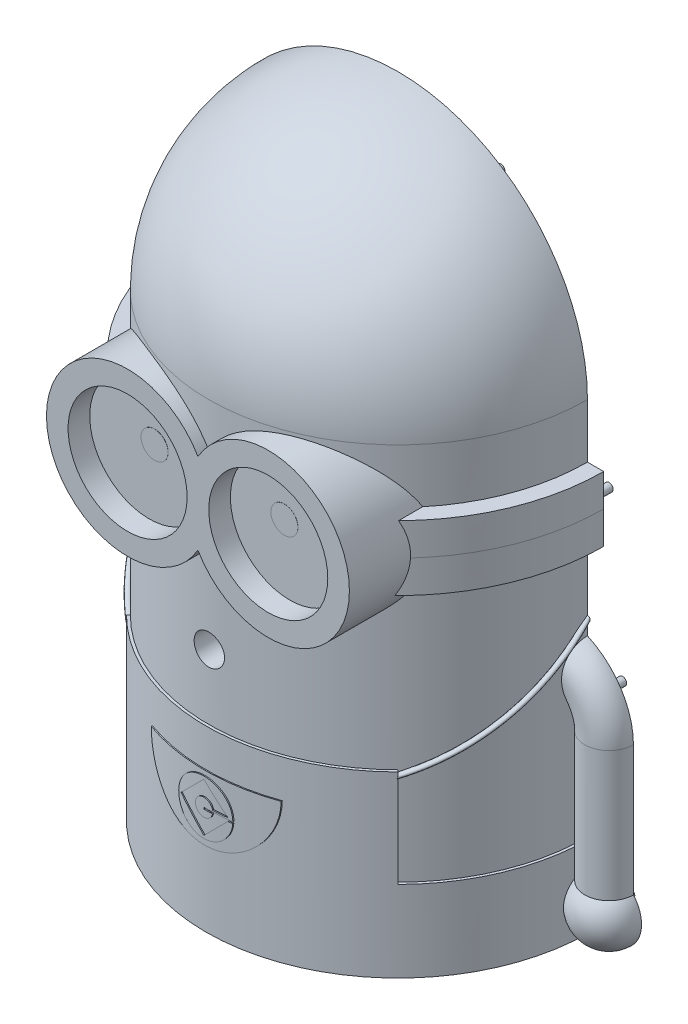
SolidWorks part; units mm, degrees
note: '?' marks a value the reader was unsure of.
material "ABS"
ref_plane "Front Plane" through (0, 0, 0) normal (0, 0, 1) x (1, 0, 0)
ref_plane "Top Plane" through (0, 0, 0) normal (0, 1, 0) x (1, 0, 0)
ref_plane "Right Plane" through (0, 0, 0) normal (1, 0, 0) x (0, 0, -1)
sketch "Sketch1" plane through (0, 0, 0) normal (0, 0, 1) x (1, 0, 0)
  line L0 (0, 0) -> (0, 101.6)
  line L1 (0, 0) -> (-44.45, 0)
  line L2 (55, 0) -> (-55, 0) construction
  line L3 (-44.45, 0) -> (-44.45, 57.15)
  line L4 (0, 72.4689) -> (0, -18.7691) construction
  arc A0 (-44.45, 57.15) -> (0, 101.6) centre (0, 57.15) cw
  dimension "D1" = 101.6
  dimension "D2" = 88.9
revolve "Body&HeadRevolve" add sketch "Sketch1" angle 360 about L4
sketch "Sketch2" plane through (0, 0, 0) normal (0, -1, 0) x (1, 0, 0)
  circle A0 centre (0, 0) radius 44.45 construction
  circle A1 centre (0, 0) radius 44.45
extrude "LowerBodyBoss-Extrude" add sketch "Sketch2" along normal blind 50.8
ref_axis "BodyAxis" through (0, -164.851, 0) along (0, 1, 0)?
ref_axis "ShoulderAxis" through (62.865, 0, 0) along (-1, 0, 0)?
sketch "Sketch4" plane through (0, 0, 0) normal (0, 0, 1) x (1, 0, 0)
  line L0 (62.865, 0) -> (-62.865, 0) construction
  line L1 (-49.53, -7.62) -> (-49.53, -40.64)
  line L2 (-36.83, -95.5054) -> (-36.83, 92.9181) construction
  line L3 (0, -164.851) -> (0, 57.15) construction
  arc A0 (-36.83, 5.08) -> (-49.53, -7.62) centre (-36.83, -7.62) ccw
  dimension "D2" = 12.7
  dimension "D1" = 33.02
  dimension "D3" = 36.83
  dimension "D4" = 5.08
ref_plane "WristPlane" through (0, -40.64, 0) normal (0, 1, 0) x (1, 0, 0)
sketch "Sketch5" plane through (0, -40.64, 0) normal (0, 1, 0) x (1, 0, 0)
  circle A0 centre (-49.53, 0) radius 5.715
  dimension "D1" = 11.43
sweep "ArmSweep" add profiles "Sketch5" path "Sketch4"
ref_axis "ArmAxis" through (-49.53, -7.62, 0) along (0, -1, 0)
sketch "Sketch7" plane through (0, 0, 0) normal (0, 0, 1) x (1, 0, 0)
  line L0 (-49.53, -7.62) -> (-49.53, -54.1089) construction
  line L1 (62.865, 0) -> (-62.865, 0) construction
  line L2 (-49.53, -35.56) -> (-49.53, -50.8)
  arc A0 (-49.53, -50.8) -> (-49.53, -35.56) centre (-49.53, -43.18) cw
  dimension "D1" = 7.62
  dimension "D2" = 43.18
revolve "HandRevolve" add sketch "Sketch7" angle 360 about axis through (-49.53, -7.62, 0) along (0, -1, 0)
mirror "ArmMirror" about plane through (0, 0, 0) normal (1, 0, 0) of "ArmSweep", "HandRevolve"
sketch "Sketch15" plane through (0, 0, 0) normal (0, 0, 1) x (1, 0, 0)
  line L0 (-16.51, 37.338) -> (0, 37.338) construction
  line L1 (0, -28.6385) -> (0, 28.6385) construction
  line L2 (16.51, 37.338) -> (0, 37.338) construction
  line L3 (-44.45, 57.15) -> (44.45, 57.15) construction
  arc A0 (0, 46.8418) -> (0, 27.8342) centre (-16.51, 37.338) ccw
  arc A1 (0, 27.8342) -> (0, 46.8418) centre (16.51, 37.338) ccw
  dimension "D1" = 38.1
  dimension "D2" = 16.51
  dimension "D3" = 19.812
extrude "GoggleBoss-Extrude" add sketch "Sketch15" along normal blind 46.99
sketch "Sketch16" plane through (0, 0, 46.99) normal (0, 0, 1) x (1, 0, 0)
  circle A0 centre (-16.51, 37.338) radius 13.97
  circle A1 centre (16.51, 37.338) radius 13.97
  arc A2 (0, 46.8418) -> (0, 27.8342) centre (-16.51, 37.338) ccw construction
  arc A3 (0, 27.8342) -> (0, 46.8418) centre (16.51, 37.338) ccw construction
  dimension "D1" = 5.08
extrude "LensCut-Extrude" cut sketch "Sketch16" against normal blind 5.08
sketch "Sketch17" plane through (0, 0, 41.91) normal (0, 0, 1) x (1, 0, 0)
  line L0 (-44.45, 57.15) -> (44.45, 57.15) construction
  line L1 (0, -28.6385) -> (0, 28.6385) construction
  circle A0 centre (-15.24, 39.116) radius 3.175
  dimension "D1" = 6.35
  dimension "D2" = 18.034
  dimension "D3" = 15.24
extrude "PupilBoss-Extrude" add sketch "Sketch17" along normal blind 0.0254
mirror "PupilMirror" about plane through (0, 0, 0) normal (1, 0, 0) of "PupilBoss-Extrude"
ref_plane "GogglePlane" through (0, 36.83, 0) normal (0, 1, 0) x (1, 0, 0)
sketch "Sketch19" plane through (0, 36.83, 0) normal (0, 1, 0) x (1, 0, 0)
  line L1 (0, 0) -> (31.4309, -31.4309)
  line L2 (0, -28.6385) -> (0, 28.6385) construction
  line L3 (0, 0) -> (0, 44.45) construction
  arc A0 (31.4309, -31.4309) -> (0, 44.45) centre (0, 0) ccw
  circle A1 centre (0, 0) radius 44.45 construction
  dimension "D2" = 45
sketch "Sketch20" plane through (0, 0, 0) normal (1, 0, 0) x (0, 0, -1)
  line L0 (44.45, 36.83) -> (44.45, 44.45)
  line L1 (44.45, 36.83) -> (-31.4309, 36.83) construction
  line L2 (44.45, -50.8) -> (44.45, 57.15) construction
  line L3 (44.45, 44.45) -> (48.26, 44.45)
  line L4 (48.26, 44.45) -> (48.26, 36.83)
  line L5 (28.6385, 36.83) -> (-28.6385, 36.83) construction
  line L6 (48.26, 36.83) -> (44.45, 36.83)
  dimension "D1" = 3.81
  dimension "D2" = 7.62
sweep "GoogleStrapSweep" add profiles "Sketch20" path "Sketch19"
mirror "StrapTopMirror" about plane through (0, 0, 0) normal (1, 0, 0) of "GoogleStrapSweep"
mirror "StrapBottomMirror" about plane through (0, 36.83, 0) normal (0, 1, 0) of "StrapTopMirror", "GoogleStrapSweep"
ref_plane "TopPantPlane" through (0, -10.16, 0) normal (0, 1, 0) x (1, 0, 0)
sketch "Sketch21" plane through (0, -10.16, 0) normal (0, 1, 0) x (1, 0, 0)
  line L0 (0, 0) -> (-31.8799, -31.8799) construction
  line L1 (0, 0) -> (0, -45.085) construction
  arc A0 (-31.8799, -31.8799) -> (0, -45.085) centre (0, 0) ccw
  dimension "D1" = 45.085
  dimension "D2" = 45
sketch "Sketch22" plane through (0, 0, 0) normal (1, 0, 0) x (0, 0, -1)
  line L0 (0, -10.16) -> (-45.085, -10.16) construction
  line L1 (-45.085, -10.16) -> (-44.45, -10.16)
  line L2 (-45.085, -10.16) -> (-45.085, -50.8)
  line L3 (-45.085, -50.8) -> (-44.45, -50.8)
  line L4 (-44.45, -10.16) -> (-44.45, -50.8)
sweep "TopPantSweep" add profiles "Sketch22" path "Sketch21"
ref_plane "BottomPantPlane" through (0, -31.75, 0) normal (0, 1, 0) x (1, 0, 0)
sketch "Sketch23" plane through (0, -31.75, 0) normal (0, 1, 0) x (1, 0, 0)
  line L0 (0, 0) -> (-45.085, 0) construction
  line L1 (0, 0) -> (-31.8799, -31.8799) construction
  arc A0 (-45.085, 0) -> (-31.8799, -31.8799) centre (0, 0) ccw
  arc A1 (-31.8799, -31.8799) -> (0, -45.085) centre (0, 0) ccw construction
sketch "Sketch24" plane through (0, 0, 0) normal (-0.7071, 0, -0.7071) x (-0.7071, 0, 0.7071)
  line L0 (45.085, -50.8) -> (44.45, -50.8) construction
  line L1 (45.085, -10.16) -> (45.085, -50.8) construction
  line L2 (44.45, -50.8) -> (44.45, -10.16) construction
  line L3 (45.085, -50.8) -> (44.45, -50.8)
  line L4 (45.085, -31.75) -> (45.085, -50.8)
  line L5 (44.45, -50.8) -> (44.45, -31.75)
  line L6 (45.085, -31.75) -> (44.45, -31.75)
  line L7 (52.415, -31.75) -> (-52.415, -31.75) construction
sweep "BottomPantSweep" add profiles "Sketch24" path "Sketch23"
ref_plane "PantStrapPlane" through (0, 12.7, 0) normal (0, 1, 0) x (1, 0, 0)
ref_axis "PantStrapAxis" through (62.865, 12.7, 0) along (-1, 0, 0)?
ref_plane "StrapTrajectoryPlane" through (0, 8.3874, 6.0143) normal (0, 0.8127, 0.5827) x (1, 0, 0)
sketch "Sketch25" plane through (0, 8.3874, 6.0143) normal (0, 0.8127, 0.5827) x (1, 0, 0)
  line L0 (62.865, 7.4007) -> (-62.865, 7.4007) construction
  line L2 (-44.45, 17.0216) -> (-44.45, 5.3288) construction
  arc A0 (-31.4309, -31.4633) -> (-44.45, 7.4007) centre (-0.5393, 0.4978) cw
  dimension "D1" = 44.45
sketch "Sketch27" plane through (0, 0, 0) normal (0, 0, 1) x (1, 0, 0)
  circle A0 centre (-44.45, 12.7) radius 0.635
  dimension "D1" = 1.27
sketch "Sketch28" plane through (0, -10.16, 0) normal (0, 1, 0) x (1, 0, 0)
  line L0 (0, -44.45) -> (0, -45.085) construction
  line L1 (-31.4309, -31.4309) -> (-31.8799, -31.8799) construction
  line L2 (0, -44.45) -> (0, -45.085)
  line L3 (-31.4309, -31.4309) -> (-31.8799, -31.8799)
  arc A0 (-31.8799, -31.8799) -> (0, -45.085) centre (0, 0) ccw construction
  arc A1 (-31.4309, -31.4309) -> (0, -44.45) centre (0, 0) ccw construction
  arc A2 (-31.8799, -31.8799) -> (0, -45.085) centre (0, 0) ccw
  arc A3 (-31.4309, -31.4309) -> (0, -44.45) centre (0, 0) ccw
extrude "Boss-Extrude1" add sketch "Sketch28" along normal blind 1.27
sweep "StrapSweep" add profiles "Sketch27" path "Sketch25"
mirror "Mirror11" about plane through (0, 0, 0) normal (0, 0, 1) of "TopPantSweep", "BottomPantSweep", "Boss-Extrude1", "StrapSweep"
mirror "Mirror12" about plane through (0, 0, 0) normal (1, 0, 0) of "Mirror11", "TopPantSweep", "BottomPantSweep", "Boss-Extrude1", "StrapSweep"
sketch "Sketch30" plane through (0, 0, 0) normal (0, 0, 1) x (1, 0, 0)
  line L0 (-15.24, -17.78) -> (15.24, -17.78)
  line L1 (0, -28.6385) -> (0, 28.6385) construction
  line L2 (31.8799, -8.89) -> (-31.8799, -8.89) construction
  arc A0 (-15.24, -17.78) -> (15.24, -17.78) centre (0, -17.78) ccw
  point P2 (0, -17.78)
  dimension "D1" = 30.48
  dimension "D2" = 8.89
extrude "Boss-Extrude2" add sketch "Sketch30" along normal offset from surface (42.7009 mm away) 0.254
sketch "Sketch31" plane through (0, 0, 0) normal (0, 0, 1) x (1, 0, 0)
  line L0 (0, -28.6385) -> (0, 28.6385) construction
  line L1 (15.24, -17.78) -> (-15.24, -17.78) construction
  line L3 (0, -30.861) -> (-5.715, -25.146)
  line L5 (-5.715, -25.146) -> (0, -19.431)
  line L6 (0, -25.146) -> (6.35, -25.146)
  line L7 (0, -25.146) -> (0, -25.527)
  line L8 (0, -25.527) -> (1.996, -25.527)
  line L9 (1.996, -24.765) -> (5.334, -24.765)
  line L10 (5.334, -25.527) -> (6.3386, -25.527)
  line L11 (0, -30.861) -> (5.715, -25.146) construction
  line L12 (0, -30.861) -> (5.334, -25.527)
  line L13 (0, -19.431) -> (5.715, -25.146) construction
  line L14 (0, -19.431) -> (5.334, -24.765)
  arc A0 (6.35, -25.146) -> (6.3386, -25.527) centre (0, -25.146) ccw
  arc A1 (1.996, -24.765) -> (1.996, -25.527) centre (0, -25.146) ccw
  dimension "D2" = 12.7
  dimension "D4" = 4.318
  dimension "D1" = 7.366
  dimension "D3" = 11.43
  dimension "D5" = 0.381
  dimension "D6" = 0.381
extrude "Boss-Extrude3" add sketch "Sketch31" along normal offset from surface (45.593 mm away) 0.254
sketch "Sketch34" plane through (0, 0, 0) normal (0, 0, 1) x (1, 0, 0)
  line L0 (0, -52.415) -> (0, 52.415) construction
  line L1 (-152.4, 152.4) -> (152.4, 152.4)
  line L2 (-152.4, 152.4) -> (-152.4, -152.4)
  line L3 (-152.4, -152.4) -> (152.4, -152.4)
  line L4 (152.4, 152.4) -> (152.4, -152.4)
  line L5 (52.415, 0) -> (-52.415, 0) construction
  point P6 (0, 152.4)
  point P9 (152.4, 0)
  dimension "D1" = 304.8
extrude "Cut-Extrude2" cut sketch "Sketch34" against normal through all
sketch "Sketch35" plane through (0, 0, 0) normal (0, 1, 0) x (1, 0, 0)
  circle A0 centre (0, 0) radius 38.1
  dimension "D1" = 38.1
extrude "Cut-Extrude3" cut sketch "Sketch35" against normal blind 50.8 and the other way blind 69.85
sketch "Sketch36" plane through (0, 0, 0) normal (0, 0, 1) x (1, 0, 0)
  line L0 (0, -27.0353) -> (0, 27.0353) construction
  line L1 (52.415, 36.83) -> (-52.415, 36.83) construction
  circle A0 centre (0, 6.35) radius 3.5719
  dimension "D1" = 7.1437
  dimension "D2" = 30.48
extrude "Cut-Extrude4" cut sketch "Sketch36" along normal through all
ref_plane "Plane1" through (0, 0, 35.56) normal (0, 0, 1) x (1, 0, 0)
ref_axis "Axis1" through (0, 6.35, 44.45) along (0, 0, -1)?
sketch "Sketch37" plane through (0, 0, 35.56) normal (0, 0, 1) x (1, 0, 0)
  circle A0 centre (0, 6.35) radius 9.8425
  circle A1 centre (0, 6.35) radius 3.5719
  circle A2 centre (0, 6.35) radius 3.5719 construction
  dimension "D1" = 19.685
extrude "Boss-Extrude4" add sketch "Sketch37" along normal up to surface (1.2467 mm away)
sketch "Sketch38" plane through (0, 0, 35.56) normal (0, 0, -1) x (-1, 0, 0)
  circle A0 centre (0, 6.35) radius 9.8425 construction
  circle A1 centre (0, 6.35) radius 9.8425
  circle A2 centre (0, 6.35) radius 9.0805
  dimension "D1" = 0.762
extrude "Boss-Extrude5" add sketch "Sketch38" along normal blind 1.27
sketch "Sketch39" plane through (0, 0, 0) normal (0, 0, -1) x (-1, 0, 0)
  line L0 (28.6385, 0) -> (-28.6385, 0) construction
  line L1 (0, 28.6385) -> (0, -28.6385) construction
  line L2 (-55.245, -38.1398) -> (-55.245, -7.62) construction
  line L5 (0, -59.7061) -> (0, 88.0359) construction
  circle A0 centre (-19.05, 88.9) radius 0.9525
  circle A1 centre (-44.45, 36.83) radius 0.9525
  circle A2 centre (-47.625, -1.0155) radius 0.9525
  circle A4 centre (-49.53, -43.18) radius 0.9525
  arc A5 (-55.245, -38.1398) -> (-45.085, -49.3692) centre (-49.53, -43.18) ccw construction
  circle A8 centre (49.53, -43.18) radius 0.9525
  circle A9 centre (47.625, -1.0155) radius 0.9525
  circle A10 centre (44.45, 36.83) radius 0.9525
  circle A11 centre (19.05, 88.9) radius 0.9525
  dimension "D1" = 1.905
  dimension "D4" = 1.905
  dimension "D5" = 1.905
  dimension "D8" = 1.905
  dimension "D2" = 88.9
  dimension "D3" = 19.05
  dimension "D6" = 7.62
  dimension "D7" = 10.16
extrude "Boss-Extrude6" add sketch "Sketch39" along normal blind 5.08
